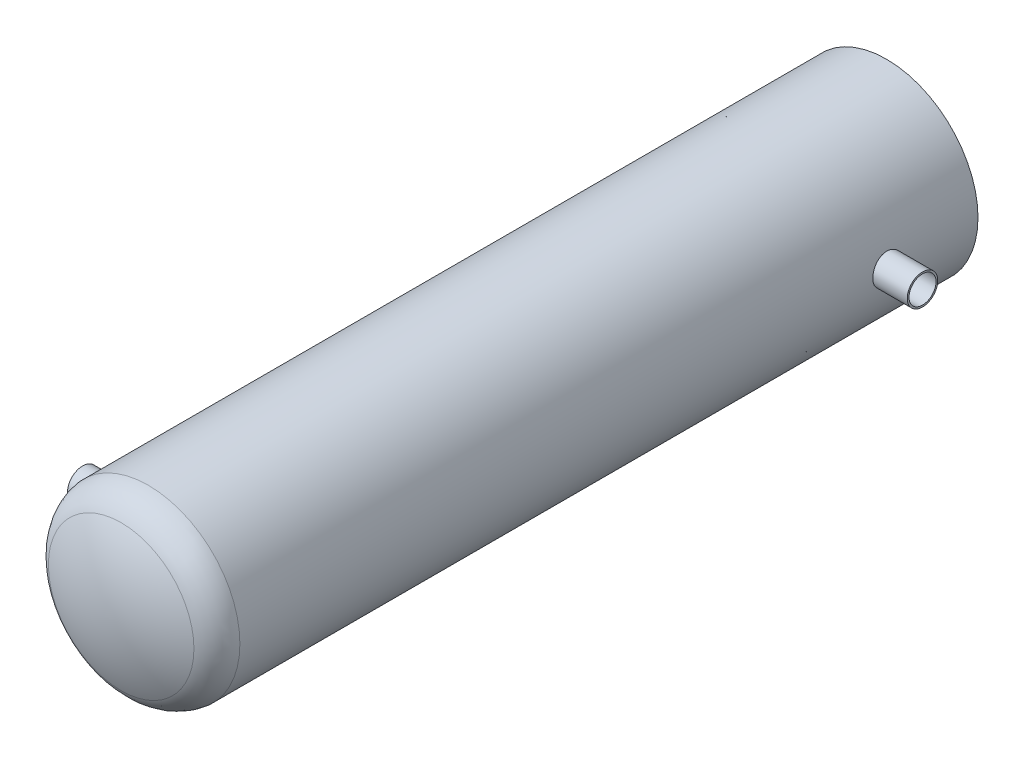
SolidWorks part; units mm, degrees
ref_plane "Front Plane" through (0, 0, 0) normal (0, 0, 1) x (1, 0, 0)
ref_plane "Top Plane" through (0, 0, 0) normal (0, 1, 0) x (1, 0, 0)
ref_plane "Right Plane" through (0, 0, 0) normal (1, 0, 0) x (0, 0, -1)
sketch "Sketch1" plane through (0, 0, 0) normal (0, 0, 1) x (1, 0, 0)
  circle A0 centre (0, 0) radius 287.52
  circle A1 centre (0, 0) radius 305
  dimension "D1" = 575.04
  dimension "D2" = 610
extrude "Boss-Extrude1" add sketch "Sketch1" along normal blind 2410
sketch "Sketch2" plane through (0, 0, 0) normal (0, 1, 0) x (1, 0, 0)
  line L0 (0, 0) -> (0, -3653.6732) construction
  line L4 (-305, -2410) -> (305, -2410) construction
  line L5 (287.52, -2410) -> (287.52, -2460)
  line L6 (-287.52, -2410) -> (287.52, -2410) construction
  line L7 (305, -2410) -> (305, -2460.9358)
  line L8 (0, -2610) -> (0, -2592.52)
  line L9 (287.52, -2410) -> (305, -2410)
  arc A0 (234.709, -2536.2372) -> (287.52, -2460) centre (190.3776, -2449.1178) ccw
  arc A1 (234.709, -2536.2372) -> (0, -2592.52) centre (0, -2074.99) cw
  arc A2 (242.6365, -2551.8162) -> (305, -2460.9358) centre (190.3776, -2449.1178) ccw
  arc A3 (242.6365, -2551.8162) -> (0, -2610) centre (0, -2074.99) cw
  dimension "D2" = 517.53
  dimension "D3" = 97.75
  dimension "D4" = 287.52
  dimension "D1" = 200
  dimension "D5" = 50
  dimension "D6" = 17.48
revolve "Revolve1" add sketch "Sketch2" angle 360 about L0
sketch "Sketch3" plane through (0, 0, 0) normal (0, 1, 0) x (1, 0, 0)
  line L0 (305, -300) -> (791.2538, -300) construction
  line L1 (305, -2460.9358) -> (305, 0) construction
  line L2 (-305, -2110.6112) -> (-762.0972, -2110.6112) construction
  line L3 (-305, 0) -> (-305, -2460.9358) construction
  line L5 (300, -254.94) -> (420, -254.94)
  line L6 (300, -254.94) -> (300, -249.2)
  line L7 (300, -249.2) -> (420, -249.2)
  line L8 (420, -254.94) -> (420, -249.2)
  point P13 (302.5648, -254.94)
  dimension "D1" = 45.06
  dimension "D2" = 50.8
  dimension "D3" = 120
  dimension "D4" = 300
  dimension "D5" = 5
revolve "Revolve2" add sketch "Sketch3" angle 360 about L0
sketch "Sketch4" plane through (0, 0, 0) normal (0, 1, 0) x (1, 0, 0)
  line L0 (-305, -2260) -> (-563.9969, -2260) construction
  line L1 (-305, 0) -> (-305, -2460.9358) construction
  line L2 (287.52, 0) -> (-287.52, 0) construction
  line L3 (-300, -2209.2) -> (-420, -2209.2)
  line L4 (-300, -2209.2) -> (-300, -2214.94)
  line L5 (-300, -2214.94) -> (-420, -2214.94)
  line L6 (-420, -2209.2) -> (-420, -2214.94)
  point P10 (-302.1342, -2209.2)
  dimension "D1" = 45.06
  dimension "D2" = 50.8
  dimension "D3" = 120
  dimension "D4" = 2260
  dimension "D5" = 5
revolve "Revolve3" add sketch "Sketch4" angle 360 about L0
sketch "Sketch5" plane through (420, 0, 0) normal (1, 0, 0) x (0, 0, -1)
  circle A0 centre (-300, 0) radius 45.06 construction
  circle A1 centre (-300, 0) radius 45.06
extrude "Cut-Extrude1" cut sketch "Sketch5" against normal blind 366
sketch "Sketch6" plane through (-420, 0, 0) normal (-1, 0, 0) x (0, 0, 1)
  circle A0 centre (2260, 0) radius 45.06 construction
  circle A1 centre (2260, 0) radius 45.06
extrude "Cut-Extrude2" cut sketch "Sketch6" against normal blind 366
sketch "Sketch7" plane through (0, 0, 0) normal (0, 1, 0) x (1, 0, 0)
  line L0 (0, -2610) -> (659.7189, -2610) construction
  arc A0 (-242.6365, -2551.8162) -> (242.6365, -2551.8162) centre (0, -2074.99) ccw construction
